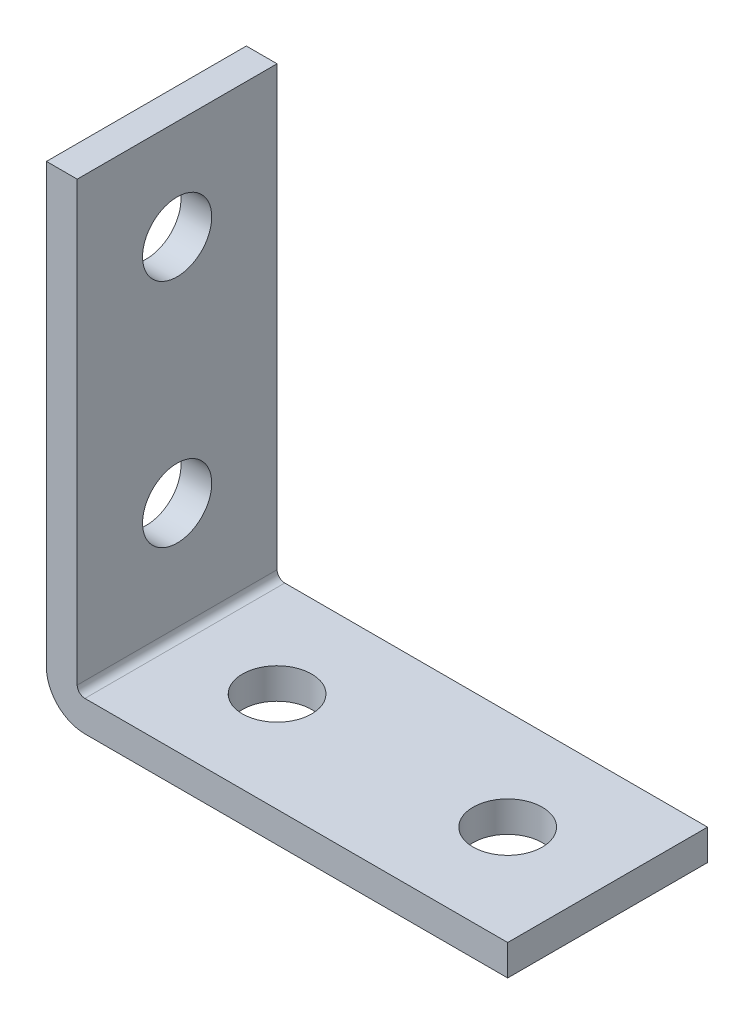
SolidWorks part; units mm, degrees
ref_plane "Front Plane" through (0, 0, 0) normal (0, 0, 1) x (1, 0, 0)
ref_plane "Top Plane" through (0, 0, 0) normal (0, 1, 0) x (1, 0, 0)
ref_plane "Right Plane" through (0, 0, 0) normal (1, 0, 0) x (0, 0, -1)
sketch "Sketch1" plane through (0, 0, 0) normal (0, 0, 1) x (1, 0, 0)
  line L0 (0, 98.425) -> (0, 7.9375)
  line L1 (7.9375, 0) -> (95.25, 0)
  arc A0 (0, 7.9375) -> (7.9375, 0) centre (7.9375, 7.9375) ccw
  dimension "D1" = 7.9375
  dimension "B" = 95.25
  dimension "A" = 98.425
extrude "Extrude-Thin1" add sketch "Sketch1" along normal mid plane 41.275 thin thin type one direction reverse wall 6.35
sketch "Sketch2" plane through (0, 6.35, 0) normal (0, 1, 0) x (1, 0, 0)
  line L0 (95.25, -20.6375) -> (95.25, 20.6375) construction
  circle A0 centre (74.6125, 0) radius 7.1438
  circle A1 centre (26.9875, 0) radius 7.1437
  dimension "Hole Size" = 14.2875
  dimension "edge" = 20.6375
  dimension "Spacing" = 47.625
extrude "Cut-Extrude1" cut sketch "Sketch2" against normal through all
sketch "Sketch3" plane through (6.35, 0, 0) normal (1, 0, 0) x (0, 0, -1)
  line L0 (-20.6375, 98.425) -> (20.6375, 98.425) construction
  circle A0 centre (0, 77.7875) radius 7.1438
  circle A1 centre (0, 30.1625) radius 7.1438
  dimension "D2" = 14.2875
  dimension "D1" = 20.6375
  dimension "D3" = 47.625
extrude "Cut-Extrude2" cut sketch "Sketch3" against normal through all
equation "\"D3@Sketch3\" = \"Spacing@Sketch2\""
equation "\"D2@Sketch3\" = \"Hole Size@Sketch2\""
